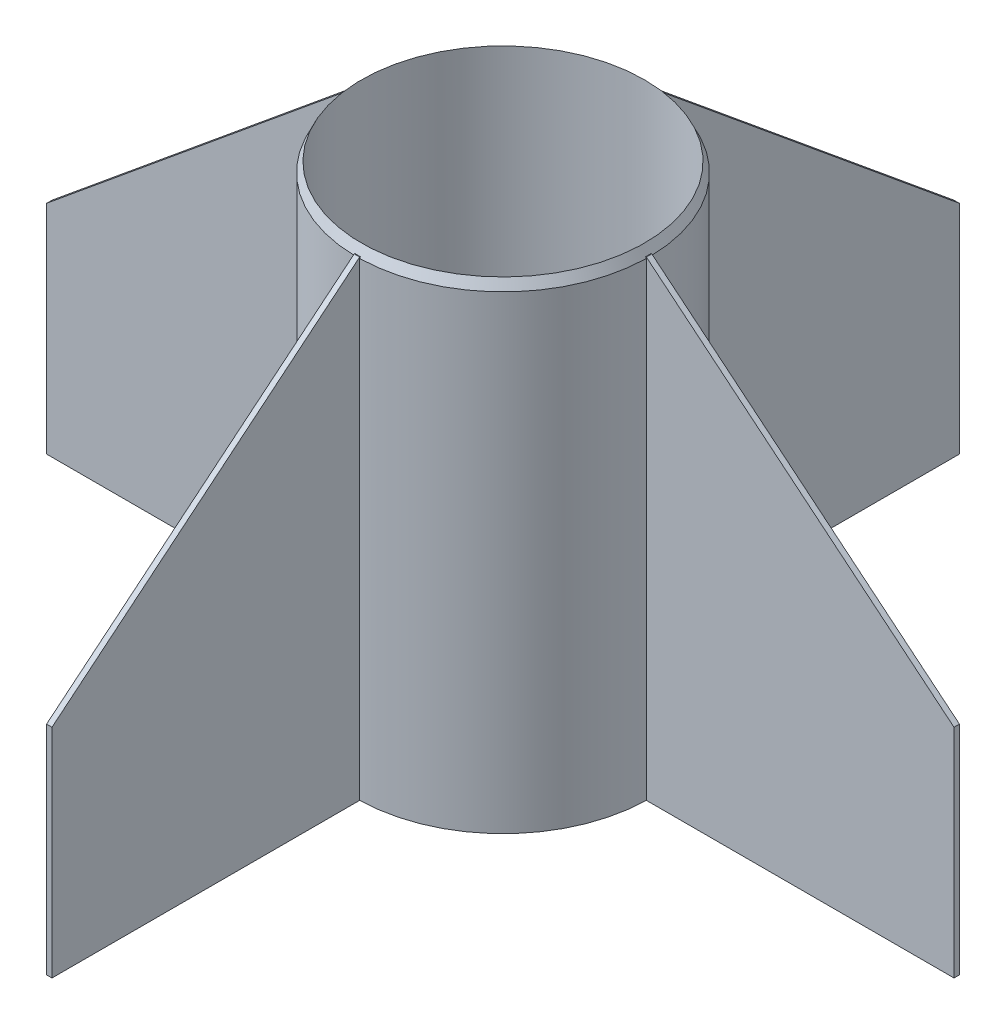
SolidWorks part; units mm, degrees
material "Commercially Pure grade 2 longitudinal (SS)"
ref_plane "Front Plane" through (0, 0, 0) normal (0, 0, 1) x (1, 0, 0)
ref_plane "Top Plane" through (0, 0, 0) normal (0, 1, 0) x (1, 0, 0)
ref_plane "Right Plane" through (0, 0, 0) normal (1, 0, 0) x (0, 0, -1)
sketch "Sketch1" plane through (0, 0, 0) normal (0, 1, 0) x (1, 0, 0)
  circle A0 centre (0, 0) radius 80.7
  circle A1 centre (0, 0) radius 78.2
  dimension "D1" = 161.4
  dimension "D2" = 156.4
extrude "Boss-Extrude1" add sketch "Sketch1" along normal blind 260
sketch "Sketch2" plane through (0, 0, 0) normal (0, 0, 1) x (1, 0, 0)
  line L0 (80.7, 0) -> (80.7, 260) construction
  line L1 (80.7, 0) -> (80.7, 260)
  line L2 (80.7, 0) -> (250.7, 0)
  line L3 (250.7, 0) -> (250.7, 120)
  line L4 (250.7, 120) -> (80.7, 260)
  dimension "D1" = 170
  dimension "D2" = 120
extrude "Boss-Extrude2" add sketch "Sketch2" along normal blind 1.5 and the other way blind 1.5 separate body
sketch "Sketch4" plane through (0, 0, 0) normal (0, 0, 1) x (1, 0, 0)
  line L0 (80.7, 260) -> (80.7, 0) construction
  line L1 (80.7, 260) -> (80.7, 0)
  line L2 (80.7, 260) -> (78.7, 260)
  line L3 (80.7, 260) -> (-80.7, 260) construction
  line L4 (78.7, 260) -> (78.7, 0)
  line L5 (-80.7, 0) -> (80.7, 0) construction
  line L6 (78.7, 0) -> (80.7, 0)
  point P2 (80.7, 130)
  dimension "D1" = 2
extrude "Boss-Extrude3" add sketch "Sketch4" along normal blind 1.5 and the other way blind 1.5
pattern_circular "CirPattern1" count 4 over 360 about axis through (0, 260, 0) along (0, -1, 0) of bodies 103
sketch "Sketch6" plane through (0, 260, 0) normal (0, 1, 0) x (1, 0, 0)
  arc A0 (80.6861, 1.5) -> (80.6861, -1.5) centre (0, 0) ccw construction
  circle A1 centre (0, 0) radius 78.2 construction
  arc A2 (80.6861, 1.5) -> (80.6861, -1.5) centre (0, 0) ccw
  circle A3 centre (0, 0) radius 78.2
  arc M2 (-1.5, 80.6861) -> (1.5, 80.6861) centre (0, 0) ccw
  circle M5 centre (0, 0) radius 78.2
extrude "Boss-Extrude4" add sketch "Sketch6" along normal blind 10 contours A2 M2 M5 region at (78.4175, 260, 0)
chamfer "Chamfer1" distance 5 angle 65 1 edges at (0, 270, 80.7) first distance on face at (0, 270, 78.2)
